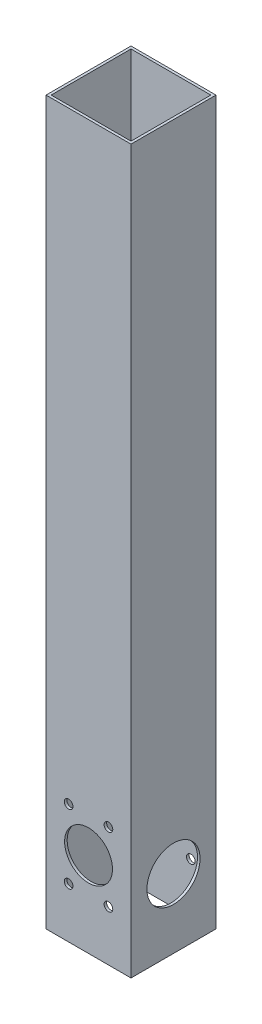
SolidWorks part; units mm, degrees
material "6061 Alloy"
ref_plane "Front Plane" through (0, 0, 0) normal (0, 0, 1) x (1, 0, 0)
ref_plane "Top Plane" through (0, 0, 0) normal (0, 1, 0) x (1, 0, 0)
ref_plane "Right Plane" through (0, 0, 0) normal (1, 0, 0) x (0, 0, -1)
sketch "Sketch1" plane through (0, 0, 0) normal (0, 1, 0) x (1, 0, 0)
  line L1 (25.4, 25.4) -> (-25.4, 25.4)
  line L2 (25.4, 25.4) -> (25.4, -25.4)
  line L3 (25.4, -25.4) -> (-25.4, -25.4)
  line L4 (-25.4, 25.4) -> (-25.4, -25.4)
  line L5 (25.4, 25.4) -> (-25.4, -25.4) construction
  line L6 (25.4, -25.4) -> (-25.4, 25.4) construction
  point P0 (0, 0)
  dimension "D1" = 50.8
extrude "Extrude-Thin1" add sketch "Sketch1" along normal blind 431.8 thin thin type one direction reverse wall 1.524
sketch "Sketch2" plane through (0, 0, 0) normal (0, 0, 1) x (1, 0, 0)
  line L0 (-36.2563, 68.2625) -> (38.5702, 68.2625) construction
  line L1 (-25.4, 0) -> (25.4, 0) construction
  line L2 (-25.4, 50.8) -> (25.4, 50.8) construction
  line L6 (25.4, 431.8) -> (25.4, 0) construction
  line L7 (-25.4, 431.8) -> (-25.4, 0) construction
  line L8 (-11.9062, 30.1778) -> (11.9063, 30.1778) construction
  line L9 (-11.9062, 71.4222) -> (11.9063, 71.4222) construction
  circle A0 centre (0, 50.8) radius 14.3002
  circle A1 centre (0, 50.8) radius 23.8125 construction
  circle A2 centre (-11.9062, 30.1778) radius 2.5908
  circle A3 centre (11.9063, 30.1778) radius 2.5908
  circle A4 centre (11.9063, 71.4222) radius 2.5908
  circle A5 centre (-11.9062, 71.4222) radius 2.5908
  point P11 (0, 50.8)
  dimension "D1" = 28.6004
  dimension "D3" = 17.4625
  dimension "D4" = 47.625
  dimension "D6" = 5.1816
  dimension "D2" = 50.8
  dimension "D5" = 60
extrude "Cut-Extrude1" cut sketch "Sketch2" along normal through all both and the other way through all
sketch "Sketch3" plane through (25.4, 0, 0) normal (1, 0, 0) x (0, 0, -1)
  line L0 (-25.4, 50.8) -> (25.4, 50.8) construction
  line L1 (-25.4, 65.1002) -> (-25.4, 36.4998) construction
  line L3 (25.4, 431.8) -> (25.4, 0) construction
  circle A0 centre (0, 41.275) radius 15.875
  point P9 (0, 50.8)
  dimension "D1" = 31.75
  dimension "D2" = 9.525
extrude "Cut-Extrude2" cut sketch "Sketch3" against normal up to surface (1.524 mm away) up to face at (23.876, 215.9, 0)
